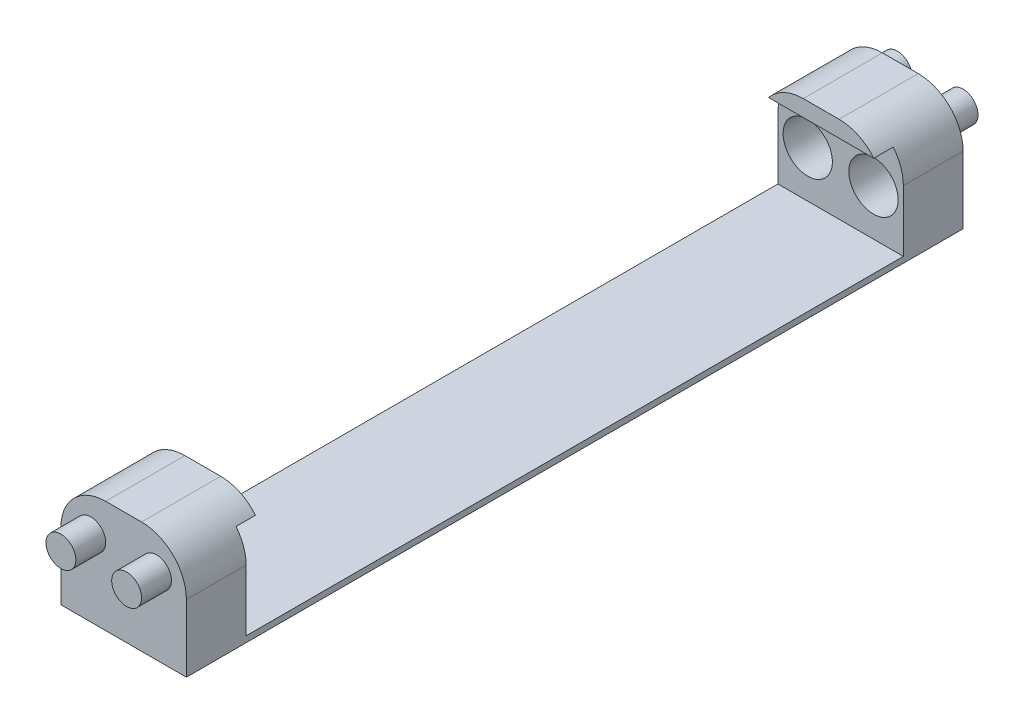
SolidWorks part; units mm, degrees
material "3003 Alloy"
ref_plane "Front Plane" through (0, 0, 0) normal (0, 0, 1) x (1, 0, 0)
ref_plane "Top Plane" through (0, 0, 0) normal (0, 1, 0) x (1, 0, 0)
ref_plane "Right Plane" through (0, 0, 0) normal (1, 0, 0) x (0, 0, -1)
sketch "Sketch1" plane through (0, 0, 0) normal (1, 0, 0) x (0, 0, -1)
  line L0 (-260, 0) -> (260, 0)
  line L1 (-220, 4) -> (220, 4)
  line L2 (0, 0) -> (0, 8) construction
  line L3 (-260, 0) -> (-260, 75)
  line L4 (-220, 4) -> (-220, 64)
  line L5 (220, 4) -> (220, 64)
  line L6 (260, 0) -> (260, 75)
  line L7 (-220, 64) -> (-207, 64)
  line L8 (-207, 64) -> (-207, 75)
  line L9 (-207, 75) -> (-260, 75)
  line L10 (220, 64) -> (207, 64)
  line L11 (207, 64) -> (207, 75)
  line L12 (207, 75) -> (260, 75)
  point P7 (0, 4)
  dimension "D1" = 520
  dimension "D2" = 440
  dimension "D3" = 4
  dimension "D4" = 75
  dimension "D5" = 60
  dimension "D6" = 13
  dimension "D7" = 13
extrude "Boss-Extrude1" add sketch "Sketch1" along normal blind 42 and the other way blind 42
fillet "Fillet1" radius 30 4 edges at (-42, 75, -233.5) (42, 75, -233.5) (-42, 75, 233.5) (42, 75, 233.5)
sketch "Sketch2" plane through (0, 0, 0) normal (0, 0, 1) x (1, 0, 0)
  line L0 (-42, 0) -> (42, 0) construction
  line L1 (42, 45) -> (42, 0) construction
  circle A0 centre (22, 35) radius 16.5
  circle A1 centre (-22, 35) radius 16.5
  dimension "D1" = 33
  dimension "D4" = 33
  dimension "D2" = 35
  dimension "D3" = 20
  dimension "D5" = 35
  dimension "D6" = 44
extrude "Cut-Extrude1" cut sketch "Sketch2" against normal blind 250 and the other way blind 250
sketch "Sketch3" plane through (0, 0, 260) normal (0, 0, 1) x (1, 0, 0)
  line L0 (42, 45) -> (42, 0) construction
  line L1 (-42, 0) -> (42, 0) construction
  line L2 (-42, 45) -> (-42, 0) construction
  circle A0 centre (22, 51) radius 10
  circle A1 centre (-22, 51) radius 10
  dimension "D1" = 20
  dimension "D4" = 20
  dimension "D2" = 20
  dimension "D3" = 51
  dimension "D5" = 51
  dimension "D6" = 20
extrude "Boss-Extrude2" add sketch "Sketch3" along normal blind 20
sketch "Sketch4" plane through (0, 0, -260) normal (0, 0, -1) x (-1, 0, 0)
  line L0 (42, 0) -> (42, 45) construction
  line L1 (42, 0) -> (-42, 0) construction
  line L2 (-42, 0) -> (-42, 45) construction
  circle A0 centre (22, 51) radius 10
  circle A1 centre (-22, 51) radius 10
  dimension "D1" = 20
  dimension "D4" = 20
  dimension "D2" = 20
  dimension "D3" = 51
  dimension "D5" = 51
  dimension "D6" = 20
extrude "Boss-Extrude3" add sketch "Sketch4" along normal blind 20
